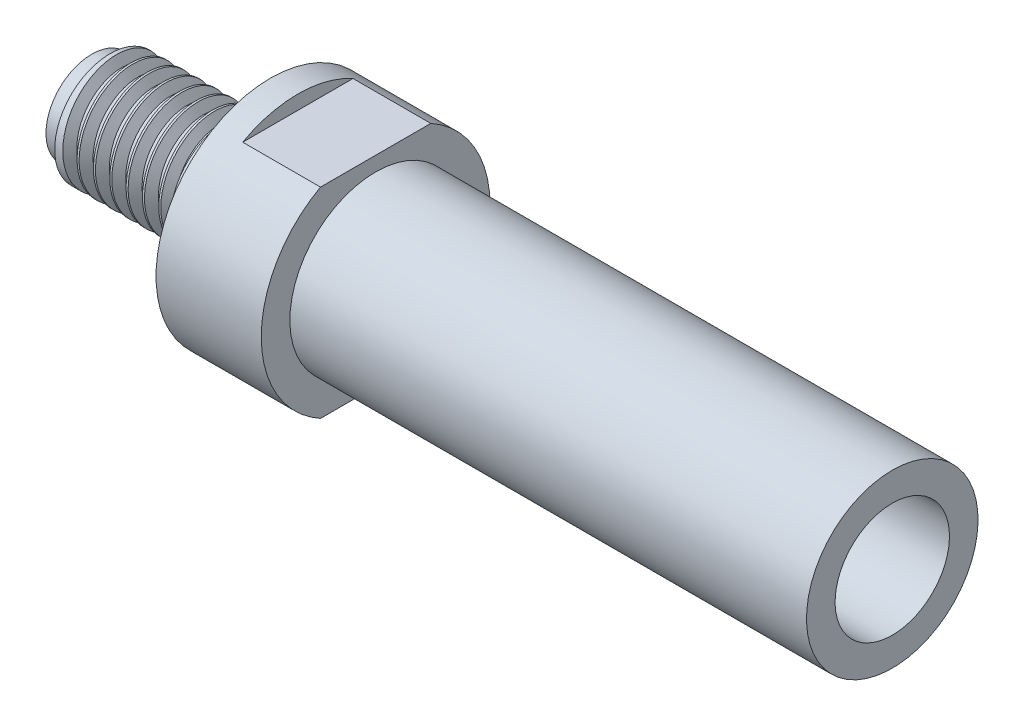
SolidWorks part; units mm, degrees
material "Free-Cutting Brass, UNS C36000"
ref_plane "Front Plane" through (0, 0, 0) normal (0, 0, 1) x (1, 0, 0)
ref_plane "Top Plane" through (0, 0, 0) normal (0, 1, 0) x (1, 0, 0)
ref_plane "Right Plane" through (0, 0, 0) normal (1, 0, 0) x (0, 0, -1)
sketch "Sketch1" plane through (0, 0, 0) normal (0, 0, 1) x (1, 0, 0)
  line L0 (0, 4.7625) -> (0, 6.35)
  line L1 (0, 0) -> (28.6861, 0)
  line L2 (0, 0) -> (0, 4.7625) construction
  line L3 (0, 4.7625) -> (28.6861, 4.7625)
  line L4 (28.6861, 0) -> (28.6861, 4.7625)
  line L8 (-5.842, 6.35) -> (-5.842, 3.1623)
  line L10 (-14.7479, 3.0734) -> (-14.7479, 2.54)
  line L11 (-14.7479, 2.54) -> (-15.7639, 2.54)
  line L12 (-15.7639, 2.54) -> (-15.7639, 0)
  line L13 (0, 0) -> (-15.7639, 0)
  line L14 (-14.7479, 3.0734) -> (-8.2233, 3.0734)
  line L15 (-8.2233, 3.0734) -> (-8.2233, 3.1623)
  line L16 (-8.2233, 3.1623) -> (-5.842, 3.1623)
  line L17 (-5.842, 6.35) -> (0, 6.35)
  dimension "D1" = 4.7625
  dimension "D2" = 6.35
  dimension "D5" = 3.1623
  dimension "D6" = 9.9219
  dimension "D7" = 1.016
  dimension "D8" = 2.54
  dimension "D9" = 44.45
  dimension "D10" = 5.842
  dimension "D11" = 3.0734
  dimension "D12" = 2.3813
revolve "Revolve1" add sketch "Sketch1" angle 360 about L13 region at (-6.408, 2.435, 0) region at (14.3431, 2.3813, 0)
sketch "Sketch2" plane through (28.6861, 0, 0) normal (1, 0, 0) x (0, 0, -1)
  circle A0 centre (0, 0) radius 1.5875
  dimension "D1" = 3.175
extrude "Cut-Extrude1" cut sketch "Sketch2" against normal through all
sketch "Sketch3" plane through (28.6861, 0, 0) normal (1, 0, 0) x (0, 0, -1)
  circle A0 centre (0, 0) radius 2.1828
  dimension "D1" = 4.3656
extrude "Cut-Extrude2" cut sketch "Sketch3" against normal blind 32.5437
sketch "Sketch4" plane through (28.6861, 0, 0) normal (1, 0, 0) x (0, 0, -1)
  circle A0 centre (0, 0) radius 3.175
  dimension "D1" = 6.35
extrude "Cut-Extrude3" cut sketch "Sketch4" against normal blind 6.35
thread "Thread1" pitch 0.9071 method cut profile "Thread Profile1" start angle 0, offset 0, length 0, pitch 0.9071, diameter 6.1468
ref_plane "Plane1" through (-14.7479, 0, -3.0734) normal (0, -1, 0) x (0, 0, -1)
sketch "Thread Profile1" plane through (-14.7479, 0, -3.0734) normal (0, -1, 0) x (0, 0, -1)
  line L0 (0, 0) -> (0, 0.9071) construction
  line L11 (0, 0) -> (0, 0.7937)
  line L12 (0, 0.7937) -> (-0.491, 0.5103)
  line L13 (-0.491, 0.5103) -> (-0.491, 0.2835)
  line L15 (-0.491, 0.2835) -> (0, 0)
  line L17 (-0.491, 0.3969) -> (0, 0.3969) construction
  point P2 (0, 0)
  dimension "Pitch" = 0.9071
  dimension "Profile_Angle" = 60
  dimension "Profile_Land" = 0.2268
  dimension "Profile_Height" = 0.491
sketch "Sketch10" plane through (0, 0, 0) normal (1, 0, 0) x (0, 0, -1)
  line L0 (-5.7785, 5.5626) -> (5.7785, 5.5626)
  line L1 (-5.7785, 5.5626) -> (-5.7785, 8.8646)
  line L2 (-5.7785, 8.8646) -> (5.7785, 8.8646)
  line L3 (5.7785, 8.8646) -> (5.7785, 5.5626)
  line L4 (-5.8417, 0) -> (5.72, 0) construction
  line L5 (0, 8.8646) -> (0, 5.5626) construction
  line L6 (0, 3.175) -> (0, -3.175) construction
  line L7 (-5.7785, 8.8646) -> (-5.7785, 5.5626)
  line L8 (5.7785, 5.5626) -> (5.7785, 8.8646)
  line L9 (0, -8.8646) -> (0, -5.5626) construction
  line L10 (5.7785, -5.5626) -> (5.7785, -8.8646)
  line L11 (-5.7785, -8.8646) -> (-5.7785, -5.5626)
  line L12 (5.7785, -8.8646) -> (5.7785, -5.5626)
  line L13 (-5.7785, -8.8646) -> (5.7785, -8.8646)
  line L14 (-5.7785, -5.5626) -> (-5.7785, -8.8646)
  line L15 (-5.7785, -5.5626) -> (5.7785, -5.5626)
  circle A0 centre (0, 0) radius 3.175 construction
  circle A1 centre (0, 0) radius 3.175 construction
  circle M5 centre (0, 0) radius 6.35
  dimension "D1" = 11.557
  dimension "D2" = 5.5626
  dimension "D3" = 3.302
extrude "Cut-Extrude4" cut sketch "Sketch10" against normal blind 4.318 contours L15 L11 L13 L10 M5 | L15 M5 | L0 M5 | L3 L2 L1 L0 M5 region at (0, 7.3381, 0) region at (0, 5.8793, 0) region at (0, -7.3381, 0) region at (0, -5.8793, 0)
